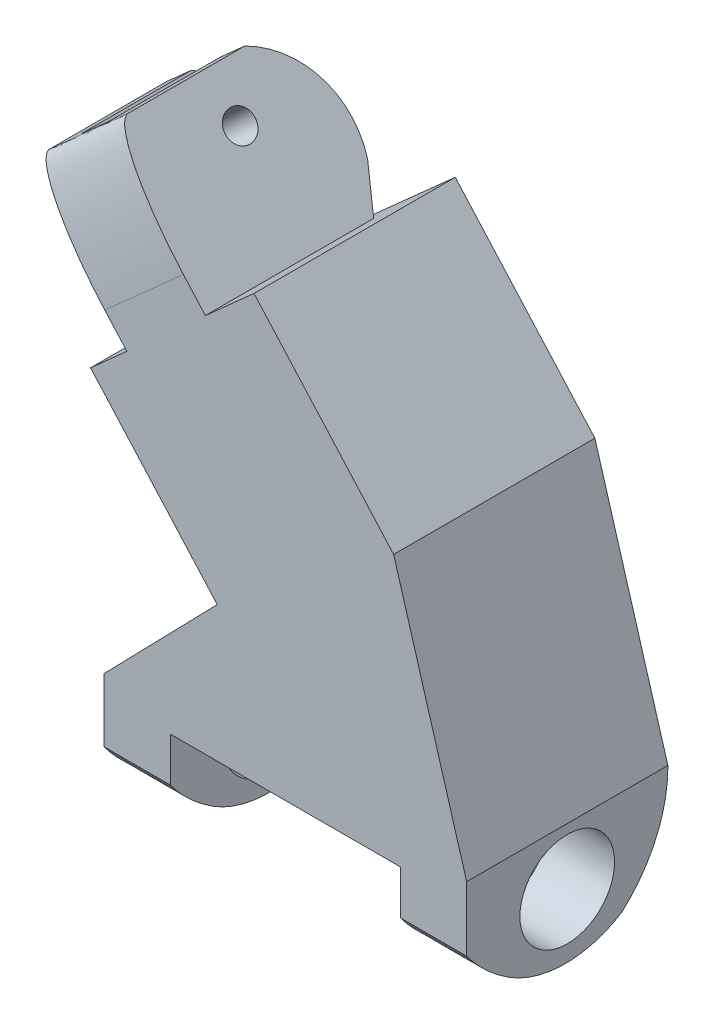
SolidWorks part; units mm, degrees
ref_plane "Plan de face" through (0, 0, 0) normal (0, 0, 1) x (1, 0, 0)
ref_plane "Plan de dessus" through (0, 0, 0) normal (0, 1, 0) x (1, 0, 0)
ref_plane "Plan de droite" through (0, 0, 0) normal (1, 0, 0) x (0, 0, -1)
sketch "Sketch1" plane through (0, 0, 0) normal (0, 0, 1) x (1, 0, 0)
  line L0 (0, 0) -> (-11.7972, 13.1953)
  line L1 (-11.7972, 13.1953) -> (-15.9072, 9.5208)
  line L2 (-15.9072, 9.5208) -> (-24.4319, 19.0557)
  line L3 (-24.4319, 19.0557) -> (-31.0668, 13.1237)
  line L4 (-31.0668, 13.1237) -> (-22.5421, 3.5888)
  line L5 (-22.5421, 3.5888) -> (-25.6061, 0.8495)
  line L6 (-25.6061, 0.8495) -> (-14.9041, -11.1209)
  line L7 (-14.9041, -11.1209) -> (-24.4642, -20.9478)
  line L8 (-24.4642, -20.9478) -> (-24.4642, -31.4378)
  line L9 (-24.4642, -31.4378) -> (-18.8642, -31.4378)
  line L10 (-18.8642, -31.4378) -> (-18.8642, -22.5778)
  line L11 (-18.8642, -22.5778) -> (0.5658, -22.5778)
  line L12 (0.5658, -22.5778) -> (0.5658, -31.4378)
  line L13 (0.5658, -31.4378) -> (6.1658, -31.4378)
  line L14 (6.1658, -31.4378) -> (6.1658, -20.8578)
  line L15 (6.1658, -20.8578) -> (0, 0)
  dimension "D1" = 8.9
  dimension "D2" = 12.79
  dimension "D3" = 12.79
  dimension "D4" = 93.99
  dimension "D5" = 5.6
  dimension "D6" = 5.6
  dimension "D7" = 19.43
  dimension "D8" = 8.86
  dimension "D9" = 8.86
  dimension "D10" = 4.11
  dimension "D11" = 4.11
  dimension "D12" = 90
  dimension "D13" = 17.7
  dimension "D14" = 154.67
  dimension "D15" = 21.75
  dimension "D16" = 10.58
  dimension "D17" = 10.49
  dimension "D18" = 13.71
extrude "Boss-Extrude1" add sketch "Sketch1" along normal blind 17
sketch "Sketch3" plane through (-4.11, -3.6745, 0) normal (0.7455, 0.6665, 0) x (0, 0, -1)
  line L0 (-1.1105, 20.9807) -> (-2.78, 17.7)
  line L1 (-17, 17.7) -> (0, 17.7) construction
  line L2 (-2.78, 17.7) -> (0.68, 17.7)
  line L3 (0.68, 17.7) -> (0.68, 32.5691)
  line L4 (0.68, 32.5691) -> (-17, 32.5691)
  line L5 (-17, 32.5691) -> (-17, 30.49)
  line L6 (-17, 30.49) -> (-5.15, 30.49)
  line L7 (-17, 30.49) -> (0, 30.49) construction
  line L8 (-17, 0) -> (-17, 17.7) construction
  arc A0 (-1.1105, 20.9807) -> (-5.15, 30.49) centre (-8.336, 23.524) ccw
  dimension "D5" = 7.66
  dimension "D1" = 11.85
  dimension "D2" = 3.46
  dimension "D3" = 17.68
  dimension "D4" = 63.03
extrude "Cut-Extrude2" cut sketch "Sketch3" against normal blind 35
sketch "Sketch4" plane through (-18.8642, 0, 0) normal (1, 0, 0) x (0, 0, -1)
  line L1 (-17, -31.4378) -> (-17, -22.5778) construction
  line L2 (-17, -26.3078) -> (-17, -22.5778)
  line L3 (-17, -22.5778) -> (-18.3389, -22.5778)
  line L4 (-18.3389, -22.5778) -> (-18.3389, -32.3097)
  line L5 (-18.3389, -32.3097) -> (1.1376, -32.3097)
  line L6 (1.1376, -32.3097) -> (1.1376, -22.5778)
  line L7 (1.1376, -22.5778) -> (0, -22.5778)
  line L8 (0, -22.5778) -> (0, -29.6578)
  line L9 (0, -31.4378) -> (0, -22.5778) construction
  line L10 (0, -29.6578) -> (-3.9, -29.6578)
  arc A1 (-3.9, -29.6578) -> (-13.4, -29.6578) centre (-8.65, -22.1313) cw
  spline S0 degree 2 poles (-13.4, -29.6578) (-15.5415, -28.2985) (-17, -26.3078) knots 0 0 0 1 1 1
  dimension "D5" = 8.9
  dimension "D1" = 3.9
  dimension "D2" = 3.73
  dimension "D3" = 7.08
  dimension "D4" = 9.5
  dimension "D6" = 3.6
extrude "Cut-Extrude3" cut sketch "Sketch4" against normal mid plane 61
sketch "Sketch5" plane through (0.5658, 0, 0) normal (-1, 0, 0) x (0, 0, 1)
  line L0 (3.9, -29.6578) -> (0, -29.6578)
  line L1 (0, -29.6578) -> (0, -20.9478)
  arc A0 (3.9, -29.6578) -> (0, -20.9478) centre (11.6762, -20.9478) cw
extrude "Cut-Extrude4" cut sketch "Sketch5" against normal blind 61
sketch "Sketch6" plane through (-24.4642, 0, 0) normal (-1, 0, 0) x (0, 0, 1)
  line L0 (0, -29.6578) -> (3.9, -29.6578) construction
  circle A0 centre (8.5, -25.6578) radius 4
  dimension "D3" = 8
  dimension "D1" = 4
  dimension "D2" = 8.5
extrude "Cut-Extrude5" cut sketch "Sketch6" against normal blind 61
sketch "Sketch7" plane through (-20.3219, 22.7302, 0) normal (-0.6665, 0.7455, 0) x (0.7455, 0.6665, 0)
  line L0 (-9.9631, -17) -> (-9.9631, -12.2961) construction
  line L1 (-5.5131, -17) -> (-14.4131, -17) construction
  line L2 (-11.6131, -14.5) -> (-8.3131, -14.5)
  line L3 (-11.6131, -14.5) -> (-11.6131, -0.2987)
  line L4 (-11.6131, -0.2987) -> (-8.3131, -0.2987)
  line L5 (-8.3131, -14.5) -> (-8.3131, -0.2987)
  point P9 (-9.9631, -14.5)
  dimension "D1" = 3.3
  dimension "D2" = 1.65
  dimension "D3" = 2.5
extrude "Cut-Extrude6" cut sketch "Sketch7" against normal up to surface (12.79 mm away) up to face at (-18.9632, 6.7886, 9.195)
sketch "Sketch8" plane through (-10.7449, -9.6065, 0) normal (-0.7455, -0.6665, 0) x (0, 0, 1)
  line L0 (17, 30.49) -> (17, 17.7) construction
  line L1 (17, 30.49) -> (5.15, 30.49) construction
  circle A0 centre (8.2, 26.49) radius 1.25
  dimension "D3" = 2.5
  dimension "D1" = 8.8
  dimension "D2" = 4
extrude "Cut-Extrude7" cut sketch "Sketch8" against normal blind 61
ref_plane "Plane1" through (-7.4275, -6.6405, 0) normal (-0.7455, -0.6665, 0) x (0, 0, 1)
sketch "Sketch9" plane through (-7.4275, -6.6405, 0) normal (-0.7455, -0.6665, 0) x (0, 0, 1)
  circle A0 centre (8.2, 26.49) radius 1.25
extrude "Extrude-Thin1" add sketch "Sketch9" along normal blind 1.75 draft 30 and the other way blind 1.75 draft 30 thin draft outward yes other way draft outward yes thin type one direction wall 1
sketch "Sketch10" plane through (-4.11, -3.6745, 0) normal (0.7455, 0.6665, 0) x (0, 0, -1)
  circle A0 centre (-8.2, 26.49) radius 1.25
extrude "Cut-Extrude9" cut sketch "Sketch10" against normal through all
fillet "Fillet1" radius 2 1 edges at (-27.7493, 16.0897, 17) second distance 10 first distance on face at (-27.7493, 16.0897, 10.45)
